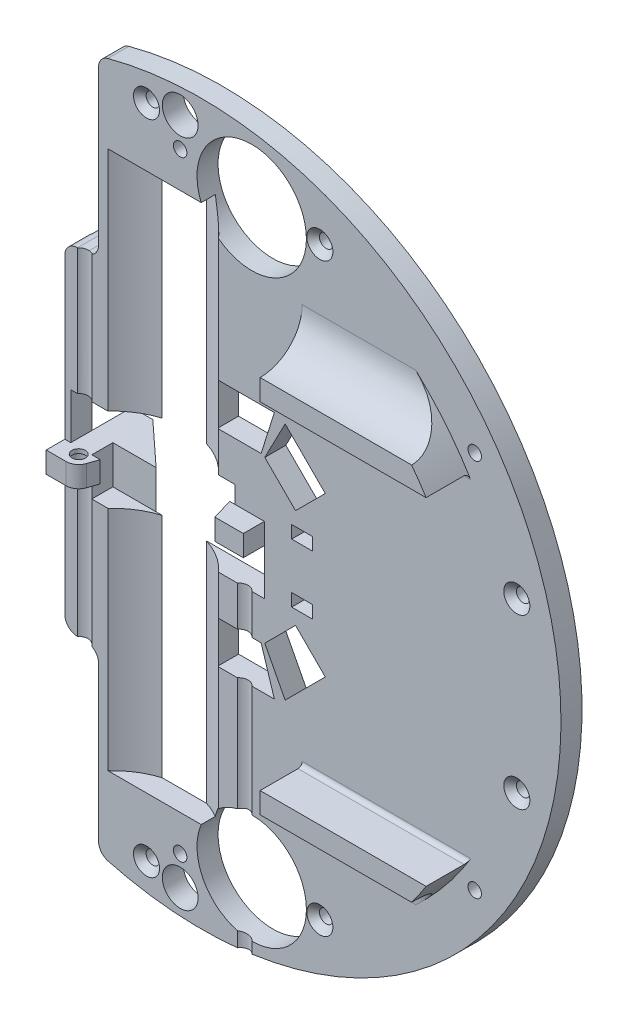
SolidWorks part; units mm, degrees
ref_plane "Front Plane" through (0, 0, 0) normal (1, 0, 0) x (0, 1, 0)
ref_plane "Top Plane" through (0, 0, 0) normal (0, 0, 1) x (0, 1, 0)
ref_plane "Right Plane" through (0, 0, 0) normal (0, 1, 0) x (-1, 0, 0)
sketch "Sketch1" plane through (0, 0, 0) normal (0, 0, 1) x (0, 1, 0)
  line L0 (0, 0) -> (0, -81.5088) construction
  line L1 (-40, 24.3888) -> (-40, 32.4114)
  line L2 (-40, 32.4114) -> (40, 32.4114)
  line L6 (-81.9478, 24.3888) -> (-40, 24.3888)
  line L7 (81.941, 24.4114) -> (40, 24.4114)
  line L8 (40, 24.4114) -> (40, 32.4114)
  arc A0 (-81.9478, 24.3888) -> (81.941, 24.4114) centre (0, 0) ccw
  circle A1 centre (-20, -75) radius 1.6
  circle A2 centre (20, -75) radius 1.6
  circle A3 centre (-69.5, -28.2) radius 1.6
  circle A9 centre (-78, 13) radius 1.6
  circle A10 centre (-79.5, 5) radius 4.25
  circle A11 centre (-69, -12) radius 13
  circle A16 centre (69, -12) radius 13
  circle A17 centre (79.5, 5) radius 4.25
  circle A18 centre (78, 13) radius 1.6
  circle A19 centre (69.5, -28.2) radius 1.6
  dimension "D1" = 171
  dimension "D3" = 3.2
  dimension "D7" = 3.2
  dimension "D8" = 78
  dimension "D13" = 5
  dimension "D14" = 69
  dimension "D16" = 40
  dimension "D2" = 75
  dimension "D4" = 20
  dimension "D5" = 69.5
  dimension "D6" = 28.2
  dimension "D9" = 40
  dimension "D10" = 13
  dimension "D11" = 8
  dimension "D12" = 79.5
  dimension "D15" = 12
extrude "Boss-Extrude2" add sketch "Sketch1" along normal blind 5
sketch "Sketch2" plane through (0, 0, 5) normal (0, 0, 1) x (1, 0, 0)
  line L1 (60, 45) -> (24, 45)
  line L3 (63.4429, 40) -> (24, 40)
  line L4 (24, 45) -> (24, 40)
  line L6 (24, -45) -> (24, -40)
  line L7 (63.4429, -40) -> (24, -40)
  line L8 (60, -45) -> (24, -45)
  arc A3 (60, -45) -> (63.4429, -40) centre (0, 0) ccw
  arc A4 (63.4429, 40) -> (60, 45) centre (0, 0) ccw
  dimension "D1" = 150
  dimension "D2" = 40
extrude "Boss-Extrude3" add sketch "Sketch2" along normal blind 10
fillet "Fillet1" radius 10 2 edges at (42, -45, 5) (42, 45, 5)
fillet "Fillet2" radius 1 2 edges at (43.7214, -40, 5) (43.7214, 40, 5)
sketch "Sketch5" plane through (0, 0, 5) normal (0, 0, 1) x (1, 0, 0)
  line L0 (0, 0) -> (93.3614, 0) construction
  circle A0 centre (65, 45) radius 1.6
  circle A2 centre (-5, 72.5) radius 1.6
  circle A4 centre (65, -45) radius 1.6
  circle A5 centre (-5, -72.5) radius 1.6
  dimension "D1" = 3.2
  dimension "D5" = 3.2
  dimension "D2" = 65
  dimension "D3" = 45
  dimension "D4" = 5
  dimension "D6" = 72.5
extrude "Cut-Extrude2" cut sketch "Sketch5" against normal blind 10
chamfer "Chamfer1" distance 1.5 angle 45 6 edges at (-14.6, -78, 5) (29.8, -69.5, 5) (76.6, -20, 5) (73.4, 20, 5) (26.6, 69.5, 5) (-11.4, 78, 5)
chamfer "Chamfer2" distance 1.5 angle 45 4 edges at (-3.4, 72.5, 0) (-3.4, -72.5, 0) (66.6, -45, 0) (66.6, 45, 0)
sketch "Sketch9" plane through (0, 0, 5) normal (0, 0, 1) x (1, 0, 0)
  line L1 (17.112, -24.1831) -> (24.1831, -17.112) construction
  line L6 (14.2376, -19.4864) -> (3.8798, -19.4864)
  line L8 (15.1085, -19.1155) -> (22.4153, -11.8087)
  line L10 (22.4153, -11.8087) -> (29.4864, -18.8798)
  line L11 (19.9404, -28.4257) -> (29.4864, -18.8798)
  line L12 (11.8087, -22.4153) -> (29.4864, -18.8798) construction
  line L13 (22.4153, -11.8087) -> (18.8798, -29.4864) construction
  line L14 (0, 0) -> (90.6538, 0) construction
  line L23 (17.3798, -29.4864) -> (3.8798, -29.4864)
  line L24 (3.8798, -19.4864) -> (3.8798, -29.4864)
  line L25 (18.8798, -19.4864) -> (3.8798, -29.4864) construction
  line L26 (18.8798, -29.4864) -> (3.8798, -19.4864) construction
  line L32 (15.1085, -19.1155) -> (19.9404, -28.4257)
  line L33 (17.3798, -29.4864) -> (14.2376, -19.4864)
  line L34 (17.3798, 29.4864) -> (14.2376, 19.4864)
  line L35 (14.2376, 19.4864) -> (3.8798, 19.4864)
  line L36 (3.8798, 19.4864) -> (3.8798, 29.4864)
  line L37 (17.3798, 29.4864) -> (3.8798, 29.4864)
  line L38 (15.1085, 19.1155) -> (19.9404, 28.4257)
  line L39 (15.1085, 19.1155) -> (22.4153, 11.8087)
  line L40 (22.4153, 11.8087) -> (29.4864, 18.8798)
  line L41 (19.9404, 28.4257) -> (29.4864, 18.8798)
  point P1 (11.3798, -24.4864)
  point P6 (20.6475, -20.6475)
  dimension "D1" = 10
  dimension "D2" = 15
  dimension "D3" = 15
  dimension "D4" = 10
  dimension "D6" = 1.5
  dimension "D7" = 1.5
extrude "Cut-Extrude3" cut sketch "Sketch9" against normal blind 10
sketch "Sketch10" plane through (0, 0, 0) normal (0, 1, 0) x (-1, 0, 0)
  line L0 (-85.5, 0) -> (24.4114, 0) construction
  circle A0 centre (9, 17) radius 17.8
  dimension "D1" = 35.6
  dimension "D2" = 17
  dimension "D3" = 9
extrude "Cut-Extrude4" cut sketch "Sketch10" against normal blind 64 and the other way blind 64
sketch "Sketch11" plane through (0, 0, 5) normal (0, 0, 1) x (1, 0, 0)
  line L0 (-26, -0.9) -> (-31, -0.9)
  line L1 (8, 10) -> (-25, 10)
  line L3 (15, -10) -> (-26, -10)
  line L4 (-26, -0.9) -> (-26, -10)
  line L5 (15, -10) -> (15, 0.9)
  line L6 (8, 10) -> (8, 0.9)
  line L7 (8, 0.9) -> (15, 0.9)
  line L8 (-31, -0.9) -> (-31, 10)
  line L9 (-31, 10) -> (-25, 10)
  point P0 (0, 0)
  dimension "D1" = 20
  dimension "D2" = 10
  dimension "D3" = 6
  dimension "D4" = 15
  dimension "D5" = 7
  dimension "D6" = 0.9
  dimension "D7" = 0.9
  dimension "D8" = 5
extrude "Cut-Extrude5" cut sketch "Sketch11" against normal blind 62.5
sketch "Sketch12" plane through (0, 0, 5) normal (0, 0, 1) x (1, 0, 0)
  line L1 (10.2402, 0) -> (10.2402, 0.9) construction
  line L2 (-6.5732, 0) -> (-6.5732, 0.9) construction
  line L3 (-6.5732, 0.9) -> (10.2402, 0.9) construction
  line L4 (-16.3028, 0) -> (-16.3028, -0.9) construction
  line L5 (-8.6264, 0) -> (-8.6264, -0.9) construction
  dimension "D1" = 0.9
  dimension "D2" = 0.9
ref_plane "Plane2" through (0, 0.9, 0) normal (0, -1, 0) x (1, 0, 0)
sketch "Sketch13" plane through (0, 0, 5) normal (0, 0, 1) x (1, 0, 0)
  line L0 (-6.5732, 0.9) -> (10.2402, 0.9) construction
  line L1 (15, 0.9) -> (6.7929, 0.9)
  line L2 (15, 0.9) -> (15, 5.9)
  line L3 (15, 5.9) -> (6.7929, 5.9)
  line L4 (6.7929, 0.9) -> (6.7929, 5.9)
  dimension "D1" = 5
extrude "Boss-Extrude4" add sketch "Sketch13" along normal blind 5
sketch "Sketch14" plane through (0, 0.9, 0) normal (0, -1, 0) x (1, 0, 0)
  circle A1 centre (10.3299, 6.4392) radius 2.25
  dimension "D2" = 4.5
extrude "Cut-Extrude6" cut sketch "Sketch14" against normal blind 4 and the other way blind 110
sketch "Sketch15" plane through (0, 0.9, 0) normal (0, -1, 0) x (1, 0, 0)
  line L2 (6.7929, 5) -> (6.7929, 10)
  line L3 (6.7929, 10) -> (8.2341, 10)
  line L4 (6.7929, 5) -> (8.2341, 10)
extrude "Cut-Extrude7" cut sketch "Sketch15" against normal blind 15
sketch "Sketch16" plane through (0, 0, 5) normal (0, 0, 1) x (1, 0, 0)
  line L0 (-32.4114, 40) -> (-32.4114, -40) construction
  line L1 (-32.4114, -0.9) -> (-24, -0.9)
  line L2 (-32.4114, -0.9) -> (-32.4114, -5.9)
  line L3 (-32.4114, -5.9) -> (-24, -5.9)
  line L4 (-24, -0.9) -> (-24, -5.9)
  dimension "D1" = 5
extrude "Boss-Extrude5" add sketch "Sketch16" along normal blind 5
sketch "Sketch17" plane through (0, -5.9, 0) normal (0, -1, 0) x (1, 0, 0)
  circle A0 centre (-27.6683, 6.4392) radius 2.25
  dimension "D1" = 4.5
extrude "Cut-Extrude8" cut sketch "Sketch17" against normal blind 4 and the other way blind 40
sketch "Sketch18" plane through (0, -5.9, 0) normal (0, -1, 0) x (1, 0, 0)
  line L0 (-24, 5) -> (-24.8314, 7.4156)
  line L1 (-32.4114, 10) -> (-24, 10) construction
  line L2 (-25.7209, 10) -> (-24, 10)
  line L3 (-24, 10) -> (-24, 5)
  line L5 (-27.6683, 9.4394) -> (-32.4114, 9.4394)
  line L6 (-32.4114, 10) -> (-32.4114, 5) construction
  line L7 (-32.4114, 9.4394) -> (-32.4114, 10)
  line L8 (-32.4114, 10) -> (-25.7209, 10)
  arc A1 (-24.8314, 7.4156) -> (-27.6683, 9.4394) centre (-27.6683, 6.4392) ccw
extrude "Cut-Extrude9" cut sketch "Sketch18" against normal blind 7
sketch "Sketch19" plane through (0, -1.9, 0) normal (0, -1, 0) x (1, 0, 0)
  circle A0 centre (-27.6683, 6.4392) radius 1.6
  dimension "D1" = 3.2
extrude "Cut-Extrude10" cut sketch "Sketch19" against normal blind 7
sketch "Sketch20" plane through (0, -0.9, 0) normal (0, 1, 0) x (-1, 0, 0)
  circle A0 centre (27.6683, 6.4392) radius 2.25
  dimension "D1" = 4.5
extrude "Cut-Extrude11" cut sketch "Sketch20" along normal blind 45
sketch "Sketch21" plane through (0, 0, 0) normal (0, 0, -1) x (1, 0, 0)
  line L1 (69.738, 4) -> (6.369, 4)
  line L2 (69.738, 4) -> (69.738, -4)
  line L3 (69.738, -4) -> (6.369, -4)
  line L4 (6.369, 4) -> (6.369, -4)
  dimension "D1" = 8
  dimension "D2" = 4
extrude "Cut-Extrude12" cut sketch "Sketch21" against normal blind 3
sketch "Sketch22" plane through (0, 0, 0) normal (0, 0, -1) x (1, 0, 0)
  line L0 (0, 0) -> (46.1564, 0) construction
  line L1 (21.5, -5.5) -> (26.5, -5.5)
  line L2 (21.5, -5.5) -> (21.5, -8.5)
  line L3 (21.5, -8.5) -> (26.5, -8.5)
  line L4 (26.5, -5.5) -> (26.5, -8.5)
  line L5 (21.5, -5.5) -> (26.5, -8.5) construction
  line L6 (21.5, -8.5) -> (26.5, -5.5) construction
  line L11 (21.5, 8.5) -> (26.5, 5.5) construction
  line L12 (21.5, 5.5) -> (26.5, 8.5) construction
  line L13 (26.5, 5.5) -> (26.5, 8.5)
  line L14 (21.5, 8.5) -> (26.5, 8.5)
  line L15 (21.5, 5.5) -> (21.5, 8.5)
  line L16 (21.5, 5.5) -> (26.5, 5.5)
  point P0 (24, -7)
  point P12 (24, 7)
  dimension "D1" = 5
  dimension "D2" = 3
  dimension "D3" = 7
  dimension "D4" = 24
extrude "Cut-Extrude13" cut sketch "Sketch22" against normal blind 5
sketch "Sketch23" plane through (0, 0, 5) normal (0, 0, 1) x (1, 0, 0)
fillet "Fillet3" radius 3 6 edges at (-24.3888, -40, 2.5) (-32.4114, -40, 2.5) (-24.4114, 40, 2.5) (-32.4114, 40, 2.5) (-24.4114, 81.941, 2.5) (-24.3888, -81.9478, 2.5)
sketch "Sketch24" plane through (0, 0, 0) normal (0, 0, -1) x (1, 0, 0)
  line L0 (-31, 0.9) -> (-31, 39.5449)
  line L1 (-26, 0.9) -> (-26, 40.3453)
  line L2 (-29.4114, 40) -> (-27.3888, 40.004)
  line L3 (-31, 0.9) -> (-26, 0.9)
  line L4 (69.738, 0) -> (25.2723, 0) construction
  line L5 (69.738, -4) -> (69.738, 4) construction
  line L7 (-29.4114, -40) -> (-27.3888, -40.004)
  line L8 (-26, -10) -> (-26, -40.3453)
  line L9 (-31, -10) -> (-31, -39.5449)
  line L10 (-31, -10) -> (-26, -10)
  line L11 (-14.2764, -10) -> (-31, -10) construction
  arc A0 (-29.4114, 40) -> (-32.4114, 37) centre (-29.4114, 37) ccw construction
  arc A1 (-29.4114, 40) -> (-31, 39.5449) centre (-29.4114, 37) ccw
  arc A2 (-27.3888, 40.004) -> (-26, 40.3453) centre (-27.3888, 43) ccw
  arc A3 (-27.3888, -40.004) -> (-26, -40.3453) centre (-27.3888, -43) cw
  arc A4 (-29.4114, -40) -> (-31, -39.5449) centre (-29.4114, -37) cw
extrude "Boss-Extrude6" add sketch "Sketch24" along normal blind 9.5
sketch "Sketch25" plane through (-31, 0, 0) normal (-1, 0, 0) x (0, -1, 0)
  line L0 (-37, 0) -> (37, 0) construction
  circle A0 centre (13, -5.25) radius 2.25
  circle A1 centre (-13, -5.25) radius 2.25
  dimension "D1" = 4.5
  dimension "D2" = 4.5
  dimension "D3" = 26
  dimension "D4" = 13
  dimension "D5" = 5.25
extrude "Cut-Extrude14" cut sketch "Sketch25" against normal blind 9.5
sketch "Sketch27" plane through (0, 10, 0) normal (0, -1, 0) x (1, 0, 0)
  line L0 (-26, -9.5) -> (-15.7165, 0)
  line L1 (-22.19, 0) -> (85.5, 0) construction
  line L2 (-26, -9.5) -> (-26, 0)
  line L3 (-26, 0) -> (-15.7165, 0)
  dimension "D1" = 14
extrude "Boss-Extrude7" add sketch "Sketch27" against normal blind 30.35
sketch "Sketch28" plane through (0, -0.9, 0) normal (0, 1, 0) x (-1, 0, 0)
  line L0 (26, -9.5) -> (15.7165, 0)
  line L1 (15.7165, 0) -> (26, 0)
  line L2 (26, 0) -> (26, -9.5)
extrude "Boss-Extrude8" add sketch "Sketch28" against normal blind 39.45
